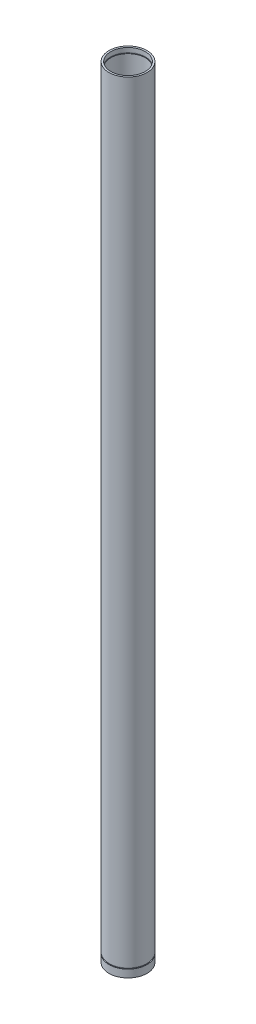
SolidWorks part; units mm, degrees
ref_plane "Front Plane" through (0, 0, 0) normal (0, 0, 1) x (1, 0, 0)
ref_plane "Top Plane" through (0, 0, 0) normal (0, 1, 0) x (1, 0, 0)
ref_plane "Right Plane" through (0, 0, 0) normal (1, 0, 0) x (0, 0, -1)
sketch "Sketch1" plane through (0, 0, 0) normal (0, 1, 0) x (1, 0, 0)
  circle A0 centre (0, 0) radius 27.1145
  circle A1 centre (0, 0) radius 24.5745
  dimension "D1" = 54.229
  dimension "D2" = 2.54
extrude "Boss-Extrude1" add sketch "Sketch1" along normal blind 1111.25
sketch "Sketch2" plane through (0, 0, 0) normal (0, 0, 1) x (1, 0, 0)
  line L0 (-27.1145, 0) -> (27.1145, 0) construction
  line L1 (22.7965, 7.62) -> (25.3365, 7.62)
  line L2 (22.7965, 7.62) -> (22.7965, 6.223)
  line L3 (22.7965, 6.223) -> (25.3365, 6.223)
  line L4 (25.3365, 7.62) -> (25.3365, 6.223)
  line L5 (24.5745, 0) -> (24.5745, 1111.25) construction
  dimension "D1" = 6.223
  dimension "D2" = 1.397
  dimension "D3" = 0.762
  dimension "D4" = 2.54
ref_axis "Axis1" through (0, 1111.25, 0) along (0, -1, 0)
revolve "Cut-Revolve1" cut sketch "Sketch2" angle 360 about axis through (0, 1111.25, 0) along (0, -1, 0)
ref_plane "Plane1" through (0, 555.625, 0) normal (0, -1, 0) x (-1, 0, 0)
mirror "Mirror1" about plane through (0, 555.625, 0) normal (0, -1, 0) of "Cut-Revolve1"
sketch "Sketch3" plane through (0, 0, 0) normal (1, 0, 0) x (0, 0, -1)
  line L1 (25.8445, 12.319) -> (27.3685, 12.319)
  line L2 (25.8445, 12.319) -> (25.8445, 10.922)
  line L3 (25.8445, 10.922) -> (27.3685, 10.922)
  line L4 (27.3685, 12.319) -> (27.3685, 10.922)
  line L5 (27.1145, 0) -> (27.1145, 1111.25) construction
  line L7 (-27.1145, 0) -> (27.1145, 0) construction
  dimension "D1" = 10.922
  dimension "D2" = 1.397
  dimension "D3" = 1.524
  dimension "D4" = 1.27
sketch "Sketch4" plane through (0, 0, 0) normal (0, 0, 1) x (1, 0, 0)
  line L0 (27.1145, 0) -> (22.6695, -33.147)
  line L1 (24.5745, 0) -> (20.1295, -33.147)
  line L2 (22.6695, -33.147) -> (20.1295, -33.147)
  line L3 (24.5745, 0) -> (27.1145, 0)
  dimension "D1" = 33.147
  dimension "D2" = 22.6695
revolve "Revolve2" [suppressed] add sketch "Sketch4" angle 360 about axis through (0, 1111.25, 0) along (0, -1, 0)
sketch "Sketch5" plane through (0, 1103.63, 0) normal (0, 1, 0) x (1, 0, 0)
  circle A0 centre (0, 0) radius 23.876
  dimension "D1" = 47.752
extrude "Boss-Extrude2" [suppressed] add sketch "Sketch5" against normal blind 12.7 separate body
sketch "Sketch6" [suppressed] plane through (0, 1103.503, 0) normal (0, 1, 0) x (1, 0, 0)
  circle A0 centre (0, 0) radius 18.034
  dimension "D1" = 36.068
extrude "Boss-Extrude4" [suppressed] add sketch "Sketch6" along normal blind 39.878 contours A0
sketch "Sketch7" [suppressed] plane through (0, 1143.381, 0) normal (0, 1, 0) x (1, 0, 0)
  circle A0 centre (0, 0) radius 7.9375
  circle A1 centre (0, 0) radius 3.175
  dimension "D1" = 6.35
  dimension "D2" = 15.875
extrude "Boss-Extrude5" [suppressed] add sketch "Sketch7" along normal blind 11.43
sketch "Sketch9" [suppressed] plane through (0, 1154.176, 0) normal (0, 1, 0) x (1, 0, 0)
  circle A0 centre (0, 0) radius 7.112
  dimension "D1" = 14.224
extrude "Boss-Extrude6" [suppressed] add sketch "Sketch9" along normal blind 9.398
sketch "Sketch10" [suppressed] plane through (0, 1102.868, 0) normal (0, 1, 0) x (1, 0, 0)
  circle A0 centre (0, 0) radius 19.05
  dimension "D1" = 38.1
extrude "Boss-Extrude7" [suppressed] add sketch "Sketch10" along normal blind 19.685
revolve "Cut-Revolve2" [suppressed] cut sketch "Sketch3" angle 360 about axis through (0, 1111.25, 0) along (0, -1, 0)
ref_plane "Plane3" [suppressed] through (0, -31.877, 0) normal (0, -1, 0) x (-1, 0, 0)
split "Split1" [suppressed] bodies to split 112
sketch "Sketch11" plane through (0, 0, 0) normal (0, 0, 1) x (1, 0, 0)
  line L0 (-27.1145, 0) -> (27.1145, 0) construction
  line L1 (27.7047, 10.922) -> (25.9715, 10.922)
  line L2 (27.7047, 10.922) -> (27.7047, 12.446)
  line L3 (27.7047, 12.446) -> (25.9715, 12.446)
  line L4 (25.9715, 10.922) -> (25.9715, 12.446)
  line L5 (27.1145, 0) -> (27.1145, 1111.25) construction
  dimension "D1" = 10.922
  dimension "D2" = 1.524
  dimension "D3" = 1.143
revolve "Cut-Revolve3" cut sketch "Sketch11" angle 360 about axis through (0, 1111.25, 0) along (0, -1, 0)
